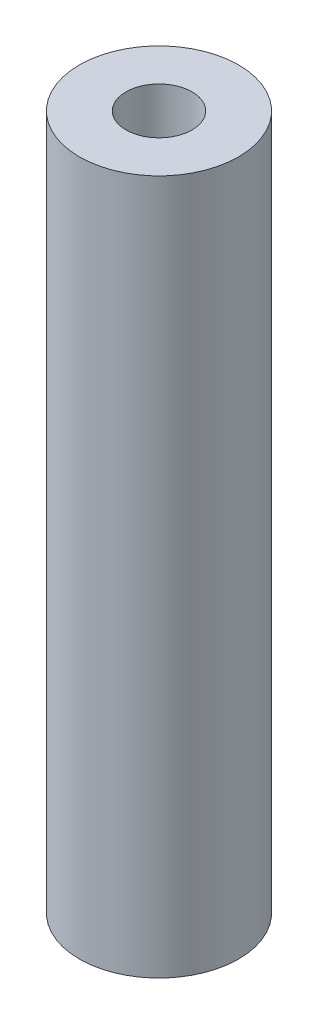
SolidWorks part; units mm, degrees
ref_plane "Front Plane" through (0, 0, 0) normal (0, 0, 1) x (1, 0, 0)
ref_plane "Top Plane" through (0, 0, 0) normal (0, 1, 0) x (1, 0, 0)
ref_plane "Right Plane" through (0, 0, 0) normal (1, 0, 0) x (0, 0, -1)
sketch "Sketch1" plane through (0, 0, 0) normal (0, 1, 0) x (1, 0, 0)
  circle A0 centre (0, 0) radius 7.415
  circle A1 centre (0, 0) radius 3.075
extrude "Boss-Extrude1" add sketch "Sketch1" along normal blind 64.7
